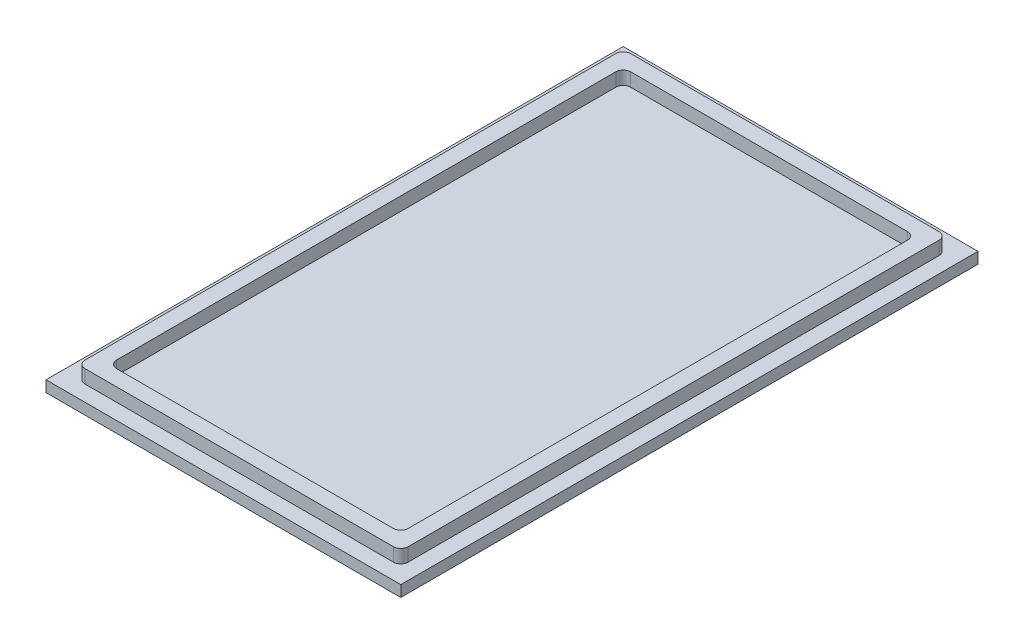
SolidWorks part; units mm, degrees
ref_plane "Front Plane" through (0, 0, 0) normal (0, 0, 1) x (1, 0, 0)
ref_plane "Top Plane" through (0, 0, 0) normal (0, 1, 0) x (1, 0, 0)
ref_plane "Right Plane" through (0, 0, 0) normal (1, 0, 0) x (0, 0, -1)
sketch "PCB Dimensions" plane through (0, 0, 0) normal (0, 1, 0) x (1, 0, 0)
  line L0 (0, 0) -> (-3.5355, 3.5355)
  line L1 (0, 0) -> (40.6457, 0)
  line L2 (0, 0) -> (0, -70.5657)
  line L3 (0, -70.5657) -> (40.6457, -70.5657)
  line L4 (40.6457, 0) -> (40.6457, -70.5657)
  line L5 (40.6457, -70.5657) -> (44.1812, -74.1012)
  line L6 (40.6457, 0) -> (44.1812, 3.5355)
  line L11 (0, -70.5657) -> (-3.5355, -74.1012)
  line L12 (44.1812, -74.1012) -> (-3.5355, -74.1012)
  line L13 (44.1812, -74.1012) -> (44.1812, 3.5355)
  line L14 (44.1812, 3.5355) -> (-3.5355, 3.5355)
  line L15 (-3.5355, -74.1012) -> (-3.5355, 3.5355)
extrude "Boss-Extrude3" add sketch "PCB Dimensions" along normal blind 1.5 contours L14 L15 L12 L13
sketch "Sketch5" plane through (0, 1.5, 0) normal (0, 1, 0) x (1, 0, 0)
  line L11 (-1.4142, 1.4142) -> (42.0599, 1.4142)
  line L12 (-1.4142, 1.4142) -> (-1.4142, -71.9799)
  line L13 (-1.4142, -71.9799) -> (42.0599, -71.9799)
  line L14 (42.0599, 1.4142) -> (42.0599, -71.9799)
  line L17 (0.7071, -0.7071) -> (39.9386, -0.7071)
  line L18 (0.7071, -0.7071) -> (0.7071, -69.8586)
  line L19 (0.7071, -69.8586) -> (39.9386, -69.8586)
  line L20 (39.9386, -0.7071) -> (39.9386, -69.8586)
extrude "Boss-Extrude4" add sketch "Sketch5" along normal blind 1.8 contours L13 L14 L11 L12 | L18 L19 L20 L17
fillet "Fillet1" radius 1 8 edges at (0.7071, 2.4, 69.8586) (-1.4142, 2.4, 71.9799) (39.9386, 2.4, 69.8586) (42.0599, 2.4, 71.9799) (0.7071, 2.4, 0.7071) (39.9386, 2.4, 0.7071) (42.0599, 2.4, -1.4142) (-1.4142, 2.4, -1.4142)
sketch "Sketch6" plane through (0, 0, 0) normal (0, -1, 0) x (1, 0, 0)
  line L0 (8.3228, 67.2497) -> (32.3228, 67.2497)
  line L1 (8.3228, 67.2497) -> (8.3228, 3.2497)
  line L2 (8.3228, 3.2497) -> (32.3228, 3.2497)
  line L3 (32.3228, 67.2497) -> (32.3228, 3.2497)
  line L4 (20.3228, 74.1012) -> (20.3228, -3.5355)
  line L5 (44.1812, 74.1012) -> (-3.5355, 74.1012) construction
  line L6 (44.1812, -3.5355) -> (-3.5355, -3.5355) construction
  line L7 (-3.5355, 35.2828) -> (44.1812, 35.2828)
  line L8 (-3.5355, 74.1012) -> (-3.5355, -3.5355) construction
  line L9 (44.1812, 74.1012) -> (44.1812, -3.5355) construction
extrude "Boss-Extrude5" add sketch "Sketch6" along normal blind 10 contours L1 L7 L4 L0 | L4 L7 L3 L0 | L7 L1 L2 L4 | L7 L4 L2 L3 region at (14.3228, 0, 51.2663) region at (26.3228, 0, 51.2663) region at (14.3228, 0, 19.2663) region at (26.3228, 0, 19.2663)
sketch "Sketch7" plane through (32.3228, 0, 0) normal (1, 0, 0) x (0, 0, -1)
  line L0 (-59.2497, 0) -> (-11.2497, 0)
  line L1 (-59.2497, 0) -> (-59.2497, -6)
  line L2 (-59.2497, -6) -> (-11.2497, -6)
  line L3 (-11.2497, 0) -> (-11.2497, -6)
extrude "Cut-Extrude1" cut sketch "Sketch7" against normal blind 24
fillet "Fillet2" radius 6 2 edges at (20.3228, -10, 3.2497) (20.3228, -10, 67.2497)
fillet "Fillet3" radius 1 2 edges at (20.3228, -6, 11.2497) (20.3228, -6, 59.2497)
